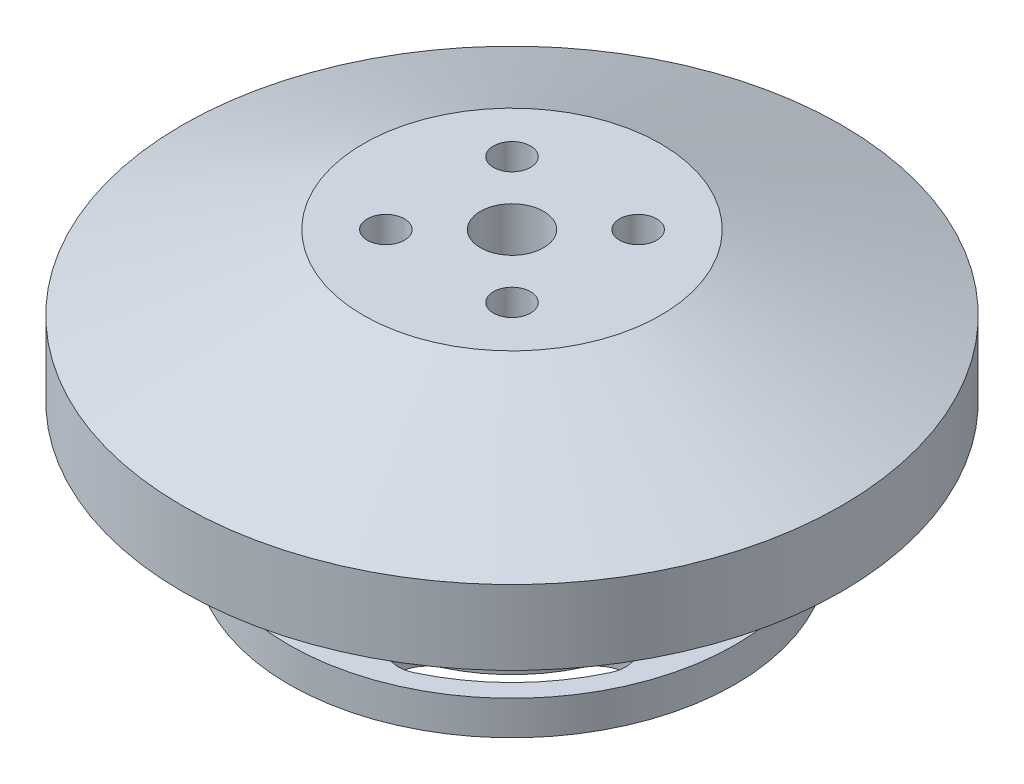
SolidWorks part; units mm, degrees
ref_plane "Plan de face" through (0, 0, 0) normal (0, 0, 1) x (1, 0, 0)
ref_plane "Plan de dessus" through (0, 0, 0) normal (0, 1, 0) x (1, 0, 0)
ref_plane "Plan de droite" through (0, 0, 0) normal (1, 0, 0) x (0, 0, -1)
sketch "Esquisse1" plane through (0, 0, 0) normal (0, 1, 0) x (1, 0, 0)
  circle A0 centre (0, 0) radius 22.175
  dimension "D1" = 44.35
extrude "Boss.-Extru.1" add sketch "Esquisse1" along normal blind 5
sketch "Esquisse2" plane through (0, 0, 0) normal (0, 0, 1) x (1, 0, 0)
  line L0 (0, 17.6967) -> (0, -9.3383) construction
  line L1 (0, 10) -> (-10, 10)
  line L2 (-10, 10) -> (-22.175, 5)
  line L3 (-22.175, 5) -> (0, 5)
  line L4 (22.175, 5) -> (-22.175, 5) construction
  line L5 (0, 5) -> (0, 10)
  dimension "D1" = 20
  dimension "D2" = 5
revolve "Révolution1" add sketch "Esquisse2" angle 360 about L0
chamfer "Chanfrein1" [suppressed] distance 0.5 angle 45
sketch "Esquisse5" [suppressed] plane through (0, 0, 0) normal (0, 0, 1) x (1, 0, 0)
  line L0 (0, 15.7888) -> (0, -12.4636) construction
  line L6 (0, 9) -> (0, 1)
  line L11 (9.8027, 9) -> (-10, 9)
  line L12 (-22.175, 1) -> (21.175, 1)
  line L13 (20.7612, 4.4996) -> (9.8027, 9)
  line L14 (21.175, 4.0858) -> (20.7612, 4.4996)
  line L15 (21.175, 1) -> (21.175, 4.0858)
  line L16 (9.8027, 9) -> (0, 9)
  line L17 (0, 1) -> (21.175, 1)
  line L18 (20.7612, 4.4996) -> (9.8027, 9)
  line L19 (21.175, 4.0858) -> (20.7612, 4.4996)
  line L20 (21.175, 1) -> (21.175, 4.0858)
  dimension "D1" = 1
revolve "Enlèvement de matière-Révolution1" [suppressed] cut sketch "Esquisse5" angle 360 about L6
sketch "Esquisse6" plane through (0, 10, 0) normal (0, 1, 0) x (1, 0, 0)
  line L0 (0, 6) -> (0, 0) construction
  line L1 (0, 0) -> (4.2426, 4.2426) construction
  circle A0 centre (0, 0) radius 6 construction
  point P3 (4.2426, 4.2426)
  point P9 (4.2426, -4.2426)
  point P10 (-4.2426, -4.2426)
  point P11 (-4.2426, 4.2426)
  point P12 (0, 0)
  dimension "D1" = 12
  dimension "D2" = 45
  dimension "D3" = 4
hole_wizard "Trou taraudé M31" positions "Esquisse3D1" profile "Esquisse7" tap size "M3" standard "ISO"
sketch3d "Esquisse3D1"
  point P0 (4.2426, 10, -4.2426)
  point P3 (4.2426, 10, 4.2426)
  point P6 (-4.2426, 10, 4.2426)
  point P9 (-4.2426, 10, -4.2426)
sketch "Esquisse7" plane through (4.2426, 10, -4.2426) normal (1, 0, 0) x (0, 0, 1)
  line L0 (0, 0) -> (0, 6.2511)
  line L1 (0, 6.2511) -> (1.25, 5.5)
  line L2 (1.25, 5.5) -> (1.25, 0)
  line L5 (1.25, 0) -> (0, 0)
  line L10 (0, 6.2511) -> (-1.25, 5.5) construction
  line L11 (0, -6.35) -> (0, 107.95) construction
  dimension "Diamètre du trou pour taraudage" = 2.5
  dimension "Profondeur du trou pour taraudage" = 5.5
  dimension "Angle de pointe" = 118
cosmetic thread "Filetage de perçage1" parameters "D1"=1, "D2"=3
cosmetic thread "Filetage de perçage2" parameters "D1"=1, "D2"=3
cosmetic thread "Filetage de perçage3" parameters "D1"=1, "D2"=3
cosmetic thread "Filetage de perçage4" parameters "D1"=1, "D2"=3
sketch "Esquisse8" [suppressed] plane through (0, 10, 0) normal (0, 1, 0) x (1, 0, 0)
  line L0 (0, 24.7209) -> (0, 0) construction
  line L1 (0, 0) -> (14.6239, 23.3628) construction
  line L2 (0, 0) -> (2.8128, 22.7623) construction
  line L3 (0, 0) -> (19.245, 12.4767) construction
  circle A3 centre (0, 0) radius 22.175 construction
  arc A4 (18.1694, 12.7124) -> (3.4948, 21.8979) centre (0, 0) ccw
  arc A5 (20.0939, -9.3789) -> (20.7115, 7.9224) centre (0, 0) ccw
  arc A6 (1.9246, -22.0913) -> (17.2167, -13.9755) centre (0, 0) ccw
  arc A7 (-18.1694, -12.7124) -> (-3.4948, -21.8979) centre (0, 0) ccw
  arc A8 (-20.0939, 9.3789) -> (-20.7115, -7.9224) centre (0, 0) ccw
  arc A9 (-1.9246, 22.0913) -> (-17.2167, 13.9755) centre (0, 0) ccw
  ellipse E0 centre (14.6239, 23.3628) end of major axis (4.5893, 7.3318) minor radius 9.3493 (3.4948, 21.8979) -> (18.1694, 12.7124) ccw
  ellipse E1 centre (28.7047, -1.0246) end of major axis (8.888, -0.3173) minor radius 9.5331 (20.7115, 7.9224) -> (20.0939, -9.3789) ccw
  ellipse E2 centre (13.465, -25.3713) end of major axis (4.1692, -7.8558) minor radius 9.5331 (17.2167, -13.9755) -> (1.9246, -22.0913) ccw
  ellipse E3 centre (-15.2397, -24.3467) end of major axis (-4.7187, -7.5386) minor radius 9.5331 (-3.4948, -21.8979) -> (-18.1694, -12.7124) ccw
  ellipse E4 centre (-28.7047, 1.0246) end of major axis (-8.888, 0.3173) minor radius 9.5331 (-20.7115, -7.9224) -> (-20.0939, 9.3789) ccw
  ellipse E5 centre (-13.465, 25.3713) end of major axis (-4.1692, 7.8558) minor radius 9.5331 (-17.2167, 13.9755) -> (-1.9246, 22.0913) ccw
  point P51 (0, 0)
  dimension "D1" = 32.044
  dimension "D2" = 25
  dimension "D3" = 6
extrude "Enlèv. mat.-Extru.1" [suppressed] cut sketch "Esquisse8" against normal blind 5.5
chamfer "Chanfrein2" [suppressed] distance 0.5 angle 45
chamfer "Chanfrein3" [suppressed] distance 0.5 angle 45
chamfer "Chanfrein4" [suppressed] distance 0.25 angle 45
sketch "Esquisse9" plane through (0, 0, 0) normal (0, -1, 0) x (1, 0, 0)
  circle A0 centre (0, 0) radius 8
  dimension "D1" = 16
extrude "Boss.-Extru.2" add sketch "Esquisse9" along normal blind 6.7 and the other way blind 5.5 separate body
sketch "Esquisse10" plane through (0, -6.7, 0) normal (0, -1, 0) x (1, 0, 0)
  circle A0 centre (0, 0) radius 15
  dimension "D1" = 30
extrude "Boss.-Extru.3" add sketch "Esquisse10" along normal blind 2.3
sketch "Esquisse11" plane through (0, -9, 0) normal (0, -1, 0) x (1, 0, 0)
  point P0 (0, 12.5)
  point P5 (12.5, 0)
  point P6 (0, -12.5)
  point P7 (-12.5, 0)
  point P8 (0, 0)
  dimension "D1" = 12.5
  dimension "D2" = 4
hole_wizard "Trou taraudé M32" positions "Esquisse3D2" profile "Esquisse12" tap size "M3" standard "ISO"
sketch3d "Esquisse3D2"
  point P0 (0, -9, 12.5)
  point P3 (12.5, -9, 0)
  point P6 (-12.5, -9, 0)
  point P9 (0, -9, -12.5)
sketch "Esquisse12" plane through (0, -9, 12.5) normal (1, 0, 0) x (0, 0, -1)
  line L0 (0, 0) -> (0, 6.2511)
  line L1 (0, 6.2511) -> (1.25, 5.5)
  line L2 (1.25, 5.5) -> (1.25, 0)
  line L5 (1.25, 0) -> (0, 0)
  line L10 (0, 6.2511) -> (-1.25, 5.5) construction
  line L11 (0, -6.35) -> (0, 107.95) construction
  dimension "Diamètre du trou pour taraudage" = 2.5
  dimension "Profondeur du trou pour taraudage" = 5.5
  dimension "Angle de pointe" = 118
cosmetic thread "Filetage de perçage5" parameters "D1"=2.3, "D2"=3
cosmetic thread "Filetage de perçage6" parameters "D1"=2.3, "D2"=3
cosmetic thread "Filetage de perçage7" parameters "D1"=2.3, "D2"=3
cosmetic thread "Filetage de perçage8" parameters "D1"=2.3, "D2"=3
sketch "Esquisse13" plane through (0, -9, 0) normal (0, -1, 0) x (1, 0, 0)
  line L0 (-8.3085, 8.3085) -> (0, 0) construction
  line L1 (0, 0) -> (0, 12.5) construction
  line L2 (-4.9658, 10.6491) -> (0, 0) construction
  line L3 (0, 0) -> (-10.6491, 4.9658) construction
  circle A0 centre (0, 0) radius 11.75 construction
  arc A1 (-10.6491, 4.9658) -> (-4.9658, 10.6491) centre (0, 0) cw construction
  arc A2 (-5.7899, 12.4164) -> (-12.4164, 5.7899) centre (0, 0) ccw
  arc A3 (-4.1417, 8.8818) -> (-8.8818, 4.1417) centre (0, 0) ccw
  arc A4 (-4.1417, 8.8818) -> (-5.7899, 12.4164) centre (-4.9658, 10.6491) ccw
  arc A5 (-12.4164, 5.7899) -> (-8.8818, 4.1417) centre (-10.6491, 4.9658) ccw
  arc A6 (4.9658, 10.6491) -> (10.6491, 4.9658) centre (0, 0) cw construction
  arc A7 (12.4164, 5.7899) -> (5.7899, 12.4164) centre (0, 0) ccw
  arc A8 (8.8818, 4.1417) -> (4.1417, 8.8818) centre (0, 0) ccw
  arc A9 (8.8818, 4.1417) -> (12.4164, 5.7899) centre (10.6491, 4.9658) ccw
  arc A10 (5.7899, 12.4164) -> (4.1417, 8.8818) centre (4.9658, 10.6491) ccw
  arc A11 (10.6491, -4.9658) -> (4.9658, -10.6491) centre (0, 0) cw construction
  arc A12 (5.7899, -12.4164) -> (12.4164, -5.7899) centre (0, 0) ccw
  arc A13 (4.1417, -8.8818) -> (8.8818, -4.1417) centre (0, 0) ccw
  arc A14 (4.1417, -8.8818) -> (5.7899, -12.4164) centre (4.9658, -10.6491) ccw
  arc A15 (12.4164, -5.7899) -> (8.8818, -4.1417) centre (10.6491, -4.9658) ccw
  arc A16 (-4.9658, -10.6491) -> (-10.6491, -4.9658) centre (0, 0) cw construction
  arc A17 (-12.4164, -5.7899) -> (-5.7899, -12.4164) centre (0, 0) ccw
  arc A18 (-8.8818, -4.1417) -> (-4.1417, -8.8818) centre (0, 0) ccw
  arc A19 (-8.8818, -4.1417) -> (-12.4164, -5.7899) centre (-10.6491, -4.9658) ccw
  arc A20 (-5.7899, -12.4164) -> (-4.1417, -8.8818) centre (-4.9658, -10.6491) ccw
  point P6 (-8.3085, 8.3085)
  point P21 (8.3085, 8.3085)
  point P28 (8.3085, -8.3085)
  point P35 (-8.3085, -8.3085)
  point P40 (0, 0)
  dimension "D1" = 23.5
  dimension "D4" = 1.95
  dimension "D2" = 45
  dimension "D3" = 40
  dimension "D5" = 4
extrude "Enlèv. mat.-Extru.2" cut sketch "Esquisse13" against normal blind 2.3
chamfer "Chanfrein5" [suppressed] distance 0.25 angle 45
sketch "Esquisse14" plane through (0, 10, 0) normal (0, 1, 0) x (1, 0, 0)
  circle A0 centre (0, 0) radius 2.125
  dimension "D1" = 4.25
extrude "Enlèv. mat.-Extru.3" cut sketch "Esquisse14" against normal through all
sketch "Esquisse15" plane through (0, 0, 0) normal (0, -1, 0) x (1, 0, 0)
  circle A0 centre (0, 0) radius 21
  dimension "D1" = 42
extrude "Enlèv. mat.-Extru.4" cut sketch "Esquisse15" against normal blind 2.3
sketch "Esquisse16" plane through (0, 5.5, 0) normal (0, 1, 0) x (1, 0, 0)
  circle A0 centre (0, 0) radius 7.5
  dimension "D1" = 15
extrude "Enlèv. mat.-Extru.5" cut sketch "Esquisse16" against normal blind 6.3 flip side to cut
chamfer "Chanfrein6" [suppressed] distance 0.25 angle 45
chamfer "Chanfrein7" [suppressed] distance 0.2 angle 45
sketch "Esquisse17" plane through (0, 10, 0) normal (0, 1, 0) x (1, 0, 0)
  circle A0 centre (0, 0) radius 2
  dimension "D1" = 4
chamfer "Chanfrein9" [suppressed] distance 0.2 angle 45
sketch "Esquisse18" [suppressed] plane through (0, 1, 0) normal (0, 1, 0) x (1, 0, 0)
  circle A1 centre (0, 0) radius 21.175
  circle A2 centre (0, 0) radius 21.175
  dimension "D1" = 0
extrude "Enlèv. mat.-Extru.6" [suppressed] cut sketch "Esquisse18" against normal blind 0.75
sketch "Esquisse19" [suppressed] plane through (0, 0.25, 0) normal (0, 1, 0) x (1, 0, 0)
  line L0 (-25.0719, 0) -> (0, 0) construction
  line L1 (0, 0) -> (-27.069, -9.8523) construction
  line L2 (-19.8075, -4.2102) -> (-19.0739, -4.0543)
  line L3 (-17.8797, -9.5068) -> (-17.2175, -9.1547)
  line L4 (-18.6419, -5.7209) -> (-7.8006, -1.775)
  line L5 (-17.9579, -7.6003) -> (-7.1166, -3.6544)
  line L6 (-19.0739, -4.0543) -> (0, 0) construction
  line L7 (-19.4743, 1) -> (-7.9373, 1)
  line L8 (-19.4743, -1) -> (-7.9373, -1)
  line L9 (-20.0529, -2.8183) -> (-19.3102, -2.7139)
  line L10 (-20.0529, 2.8183) -> (-19.3102, 2.7139)
  line L11 (-17.9579, 7.6003) -> (-7.1166, 3.6544)
  line L12 (-18.6419, 5.7209) -> (-7.8006, 1.775)
  line L13 (-19.8075, 4.2102) -> (-19.0739, 4.0543)
  line L14 (-17.8797, 9.5068) -> (-17.2175, 9.1547)
  line L15 (-14.2754, 13.2839) -> (-5.4375, 5.868)
  line L16 (-15.561, 11.7518) -> (-6.7231, 4.3359)
  line L17 (-17.173, 10.7309) -> (-16.5369, 10.3334)
  line L18 (-13.5499, 15.0487) -> (-13.048, 14.4913)
  line L19 (-8.8711, 17.3653) -> (-3.1026, 7.3739)
  line L20 (-10.6032, 16.3653) -> (-4.8347, 6.3739)
  line L21 (-12.4671, 15.9572) -> (-12.0054, 15.3662)
  line L22 (-7.5858, 18.7755) -> (-7.3048, 18.0801)
  line L23 (-2.3969, 19.3521) -> (-0.3935, 7.9903)
  line L24 (-4.3665, 19.0048) -> (-2.3631, 7.643)
  line L25 (-6.2576, 19.2589) -> (-6.0258, 18.5456)
  line L26 (-0.7067, 20.2377) -> (-0.6805, 19.4881)
  line L27 (4.3665, 19.0048) -> (2.3631, 7.643)
  line L28 (2.3969, 19.3521) -> (0.3935, 7.9903)
  line L29 (0.7067, 20.2377) -> (0.6805, 19.4881)
  line L30 (6.2576, 19.2589) -> (6.0258, 18.5456)
  line L31 (10.6032, 16.3653) -> (4.8347, 6.3739)
  line L32 (8.8711, 17.3653) -> (3.1026, 7.3739)
  line L33 (7.5858, 18.7755) -> (7.3048, 18.0801)
  line L34 (12.4671, 15.9572) -> (12.0054, 15.3662)
  line L35 (15.561, 11.7518) -> (6.7231, 4.3359)
  line L36 (14.2754, 13.2839) -> (5.4375, 5.868)
  line L37 (13.5499, 15.0487) -> (13.048, 14.4913)
  line L38 (17.173, 10.7309) -> (16.5369, 10.3334)
  line L39 (18.6419, 5.7209) -> (7.8006, 1.775)
  line L40 (17.9579, 7.6003) -> (7.1166, 3.6544)
  line L41 (17.8797, 9.5068) -> (17.2175, 9.1547)
  line L42 (19.8075, 4.2102) -> (19.0739, 4.0543)
  line L43 (19.4743, -1) -> (7.9373, -1)
  line L44 (19.4743, 1) -> (7.9373, 1)
  line L45 (20.0529, 2.8183) -> (19.3102, 2.7139)
  line L46 (20.0529, -2.8183) -> (19.3102, -2.7139)
  line L47 (17.9579, -7.6003) -> (7.1166, -3.6544)
  line L48 (18.6419, -5.7209) -> (7.8006, -1.775)
  line L49 (19.8075, -4.2102) -> (19.0739, -4.0543)
  line L50 (17.8797, -9.5068) -> (17.2175, -9.1547)
  line L51 (14.2754, -13.2839) -> (5.4375, -5.868)
  line L52 (15.561, -11.7518) -> (6.7231, -4.3359)
  line L53 (17.173, -10.7309) -> (16.5369, -10.3334)
  line L54 (13.5499, -15.0487) -> (13.048, -14.4913)
  line L55 (8.8711, -17.3653) -> (3.1026, -7.3739)
  line L56 (10.6032, -16.3653) -> (4.8347, -6.3739)
  line L57 (12.4671, -15.9572) -> (12.0054, -15.3662)
  line L58 (7.5858, -18.7755) -> (7.3048, -18.0801)
  line L59 (2.3969, -19.3521) -> (0.3935, -7.9903)
  line L60 (4.3665, -19.0048) -> (2.3631, -7.643)
  line L61 (6.2576, -19.2589) -> (6.0258, -18.5456)
  line L62 (0.7067, -20.2377) -> (0.6805, -19.4881)
  line L63 (-4.3665, -19.0048) -> (-2.3631, -7.643)
  line L64 (-2.3969, -19.3521) -> (-0.3935, -7.9903)
  line L65 (-0.7067, -20.2377) -> (-0.6805, -19.4881)
  line L66 (-6.2576, -19.2589) -> (-6.0258, -18.5456)
  line L67 (-10.6032, -16.3653) -> (-4.8347, -6.3739)
  line L68 (-8.8711, -17.3653) -> (-3.1026, -7.3739)
  line L69 (-7.5858, -18.7755) -> (-7.3048, -18.0801)
  line L70 (-12.4671, -15.9572) -> (-12.0054, -15.3662)
  line L71 (-15.561, -11.7518) -> (-6.7231, -4.3359)
  line L72 (-14.2754, -13.2839) -> (-5.4375, -5.868)
  line L73 (-13.5499, -15.0487) -> (-13.048, -14.4913)
  line L74 (-17.173, -10.7309) -> (-16.5369, -10.3334)
  arc A0 (-19.8075, -4.2102) -> (-17.8797, -9.5068) centre (0, 0) ccw
  arc A1 (-19.0739, -4.0543) -> (-18.6419, -5.7209) centre (0, 0) ccw
  circle A2 centre (0, 0) radius 8 construction
  arc A3 (-17.9579, -7.6003) -> (-17.2175, -9.1547) centre (0, 0) ccw
  arc A4 (-19.4743, -1) -> (-19.3102, -2.7139) centre (0, 0) ccw
  arc A5 (-20.0529, 2.8183) -> (-20.0529, -2.8183) centre (0, 0) ccw
  arc A6 (-19.3102, 2.7139) -> (-19.4743, 1) centre (0, 0) ccw
  arc A7 (-18.6419, 5.7209) -> (-19.0739, 4.0543) centre (0, 0) ccw
  arc A8 (-17.8797, 9.5068) -> (-19.8075, 4.2102) centre (0, 0) ccw
  arc A9 (-17.2175, 9.1547) -> (-17.9579, 7.6003) centre (0, 0) ccw
  arc A10 (-15.561, 11.7518) -> (-16.5369, 10.3334) centre (0, 0) ccw
  arc A11 (-13.5499, 15.0487) -> (-17.173, 10.7309) centre (0, 0) ccw
  arc A12 (-13.048, 14.4913) -> (-14.2754, 13.2839) centre (0, 0) ccw
  arc A13 (-10.6032, 16.3653) -> (-12.0054, 15.3662) centre (0, 0) ccw
  arc A14 (-7.5858, 18.7755) -> (-12.4671, 15.9572) centre (0, 0) ccw
  arc A15 (-7.3048, 18.0801) -> (-8.8711, 17.3653) centre (0, 0) ccw
  arc A16 (-4.3665, 19.0048) -> (-6.0258, 18.5456) centre (0, 0) ccw
  arc A17 (-0.7067, 20.2377) -> (-6.2576, 19.2589) centre (0, 0) ccw
  arc A18 (-0.6805, 19.4881) -> (-2.3969, 19.3521) centre (0, 0) ccw
  arc A19 (2.3969, 19.3521) -> (0.6805, 19.4881) centre (0, 0) ccw
  arc A20 (6.2576, 19.2589) -> (0.7067, 20.2377) centre (0, 0) ccw
  arc A21 (6.0258, 18.5456) -> (4.3665, 19.0048) centre (0, 0) ccw
  arc A22 (8.8711, 17.3653) -> (7.3048, 18.0801) centre (0, 0) ccw
  arc A23 (12.4671, 15.9572) -> (7.5858, 18.7755) centre (0, 0) ccw
  arc A24 (12.0054, 15.3662) -> (10.6032, 16.3653) centre (0, 0) ccw
  arc A25 (14.2754, 13.2839) -> (13.048, 14.4913) centre (0, 0) ccw
  arc A26 (17.173, 10.7309) -> (13.5499, 15.0487) centre (0, 0) ccw
  arc A27 (16.5369, 10.3334) -> (15.561, 11.7518) centre (0, 0) ccw
  arc A28 (17.9579, 7.6003) -> (17.2175, 9.1547) centre (0, 0) ccw
  arc A29 (19.8075, 4.2102) -> (17.8797, 9.5068) centre (0, 0) ccw
  arc A30 (19.0739, 4.0543) -> (18.6419, 5.7209) centre (0, 0) ccw
  arc A31 (19.4743, 1) -> (19.3102, 2.7139) centre (0, 0) ccw
  arc A32 (20.0529, -2.8183) -> (20.0529, 2.8183) centre (0, 0) ccw
  arc A33 (19.3102, -2.7139) -> (19.4743, -1) centre (0, 0) ccw
  arc A34 (18.6419, -5.7209) -> (19.0739, -4.0543) centre (0, 0) ccw
  arc A35 (17.8797, -9.5068) -> (19.8075, -4.2102) centre (0, 0) ccw
  arc A36 (17.2175, -9.1547) -> (17.9579, -7.6003) centre (0, 0) ccw
  arc A37 (15.561, -11.7518) -> (16.5369, -10.3334) centre (0, 0) ccw
  arc A38 (13.5499, -15.0487) -> (17.173, -10.7309) centre (0, 0) ccw
  arc A39 (13.048, -14.4913) -> (14.2754, -13.2839) centre (0, 0) ccw
  arc A40 (10.6032, -16.3653) -> (12.0054, -15.3662) centre (0, 0) ccw
  arc A41 (7.5858, -18.7755) -> (12.4671, -15.9572) centre (0, 0) ccw
  arc A42 (7.3048, -18.0801) -> (8.8711, -17.3653) centre (0, 0) ccw
  arc A43 (4.3665, -19.0048) -> (6.0258, -18.5456) centre (0, 0) ccw
  arc A44 (0.7067, -20.2377) -> (6.2576, -19.2589) centre (0, 0) ccw
  arc A45 (0.6805, -19.4881) -> (2.3969, -19.3521) centre (0, 0) ccw
  arc A46 (-2.3969, -19.3521) -> (-0.6805, -19.4881) centre (0, 0) ccw
  arc A47 (-6.2576, -19.2589) -> (-0.7067, -20.2377) centre (0, 0) ccw
  arc A48 (-6.0258, -18.5456) -> (-4.3665, -19.0048) centre (0, 0) ccw
  arc A49 (-8.8711, -17.3653) -> (-7.3048, -18.0801) centre (0, 0) ccw
  arc A50 (-12.4671, -15.9572) -> (-7.5858, -18.7755) centre (0, 0) ccw
  arc A51 (-12.0054, -15.3662) -> (-10.6032, -16.3653) centre (0, 0) ccw
  arc A52 (-14.2754, -13.2839) -> (-13.048, -14.4913) centre (0, 0) ccw
  arc A53 (-17.173, -10.7309) -> (-13.5499, -15.0487) centre (0, 0) ccw
  arc A54 (-16.5369, -10.3334) -> (-15.561, -11.7518) centre (0, 0) ccw
  arc A55 (-7.1166, -3.6544) -> (-6.7231, -4.3359) centre (0, 0) ccw
  arc A56 (-7.9373, -1) -> (-7.8006, -1.775) centre (0, 0) ccw
  arc A57 (-7.8006, 1.775) -> (-7.9373, 1) centre (0, 0) ccw
  arc A58 (-6.7231, 4.3359) -> (-7.1166, 3.6544) centre (0, 0) ccw
  arc A59 (-4.8347, 6.3739) -> (-5.4375, 5.868) centre (0, 0) ccw
  arc A60 (-2.3631, 7.643) -> (-3.1026, 7.3739) centre (0, 0) ccw
  arc A61 (0.3935, 7.9903) -> (-0.3935, 7.9903) centre (0, 0) ccw
  arc A62 (3.1026, 7.3739) -> (2.3631, 7.643) centre (0, 0) ccw
  arc A63 (5.4375, 5.868) -> (4.8347, 6.3739) centre (0, 0) ccw
  arc A64 (7.1166, 3.6544) -> (6.7231, 4.3359) centre (0, 0) ccw
  arc A65 (7.9373, 1) -> (7.8006, 1.775) centre (0, 0) ccw
  arc A66 (7.8006, -1.775) -> (7.9373, -1) centre (0, 0) ccw
  arc A67 (6.7231, -4.3359) -> (7.1166, -3.6544) centre (0, 0) ccw
  arc A68 (4.8347, -6.3739) -> (5.4375, -5.868) centre (0, 0) ccw
  arc A69 (2.3631, -7.643) -> (3.1026, -7.3739) centre (0, 0) ccw
  arc A70 (-0.3935, -7.9903) -> (0.3935, -7.9903) centre (0, 0) ccw
  arc A71 (-3.1026, -7.3739) -> (-2.3631, -7.643) centre (0, 0) ccw
  arc A72 (-5.4375, -5.868) -> (-4.8347, -6.3739) centre (0, 0) ccw
  point P153 (0, 0)
  point P187 (0, 0)
  dimension "D2" = 20.25
  dimension "D4" = 16
  dimension "D1" = 20
  dimension "D3" = 0.75
  dimension "D5" = 2
  dimension "D6" = 1
  dimension "D7" = 8
  dimension "D8" = 18
  dimension "D9" = 18
extrude "Boss.-Extru.5" [suppressed] add sketch "Esquisse19" along normal blind 3.75 separate body
ref_plane "Plan2" [suppressed] through (-9.7372, 0, 16.8653) normal (-0.5, 0, 0.866) x (0.866, 0, 0.5)
ref_plane "Plan3" [suppressed] through (-9.4872, 0, 16.4323) normal (-0.5, 0, 0.866) x (0.866, 0, 0.5)
sketch "Esquisse21" [suppressed] plane through (-9.4872, 0, 16.4323) normal (-0.5, 0, 0.866) x (0.866, 0, 0.5)
  line L0 (2.8183, 4) -> (-2.8183, 4) construction
  line L1 (-1, 4.5) -> (1, 4.5)
  line L2 (-1.5, 4) -> (-1.5, 0.25)
  line L3 (-1, -0.25) -> (1, -0.25)
  line L4 (1.5, 4) -> (1.5, 0.25)
  line L5 (-1, 4) -> (-1, 0.25) construction
  line L6 (-2.8183, 0.25) -> (2.8183, 0.25) construction
  line L7 (1, 4) -> (1, 0.25) construction
  arc A0 (-1.5, 0.25) -> (-1, -0.25) centre (-1, 0.25) ccw
  arc A1 (1, -0.25) -> (1.5, 0.25) centre (1, 0.25) ccw
  arc A2 (1, 4.5) -> (1.5, 4) centre (1, 4) cw
  arc A3 (-1, 4.5) -> (-1.5, 4) centre (-1, 4) ccw
  dimension "D5" = 0.5
  dimension "D1" = 0.5
  dimension "D2" = 0.5
  dimension "D3" = 0.5
  dimension "D4" = 0.5
ref_plane "Plan4" [suppressed] through (-8.1881, 4, 17.1823) normal (0, -1, 0) x (-1, 0, 0)
sketch "Esquisse22" [suppressed] plane through (-8.1881, 4, 17.1823) normal (0, -1, 0) x (-1, 0, 0)
  circle A0 centre (0, 0) radius 0.375
  dimension "D1" = 0.75
sweep "Balayage3" [suppressed] add profiles "Esquisse22" path "Esquisse21"
pattern_linear "Répétition linéaire3" [suppressed] count 15 spacing 0.7 of bodies 117
pattern_circular "Répétition circulaire3" [suppressed] count 18 every 20 of bodies 146 145 144 143 142 141 140 139 138 137 136 135 134 133 117
